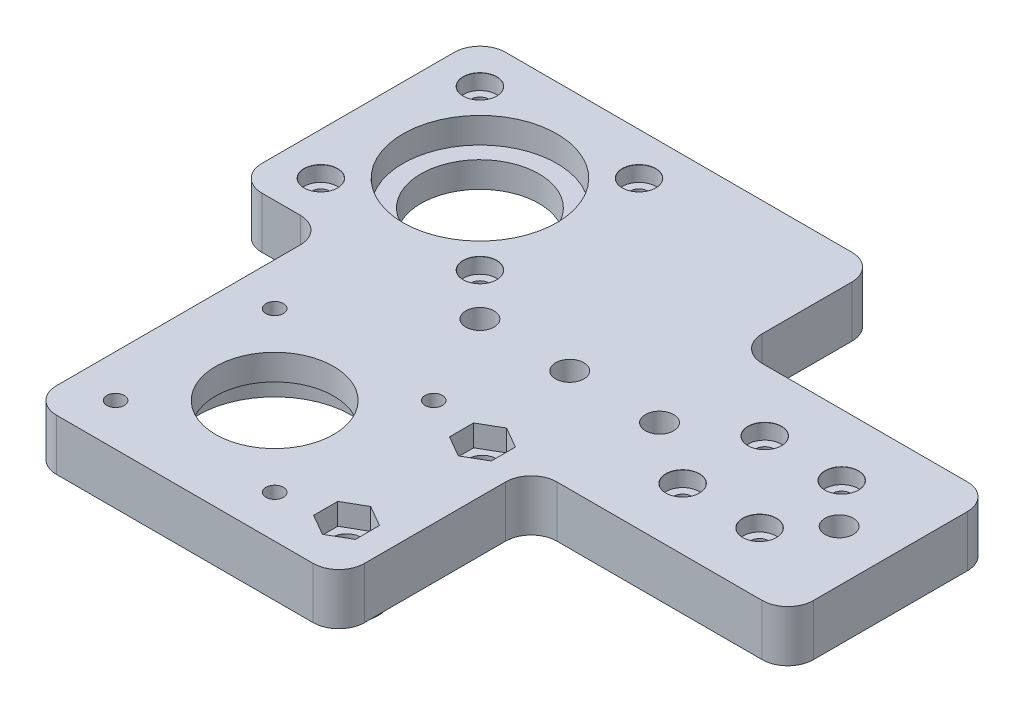
SolidWorks part; units mm, degrees
ref_plane "Front Plane" through (0, 0, 0) normal (0, 0, 1) x (1, 0, 0)
ref_plane "Top Plane" through (0, 0, 0) normal (0, 1, 0) x (1, 0, 0)
ref_plane "Right Plane" through (0, 0, 0) normal (1, 0, 0) x (0, 0, -1)
sketch "Sketch1" plane through (0, 0, 0) normal (0, 1, 0) x (1, 0, 0)
  line L0 (0, 0) -> (110, 0) construction
  line L1 (110, 0) -> (110, 20) construction
  line L2 (110, 20) -> (0, 20) construction
  line L3 (0, 20) -> (0, 0) construction
  line L4 (110, 30) -> (110, -10) construction
  line L5 (110, 30) -> (80, 30) construction
  line L6 (80, 30) -> (80, -10) construction
  line L7 (80, -10) -> (110, -10) construction
  line L8 (0, 67.5) -> (0, -47.5)
  line L16 (0, 67.5) -> (60, 67.5)
  line L18 (0, -47.5) -> (60, -47.5)
  line L19 (60, 67.5) -> (60, 30)
  line L22 (110, -10) -> (60, -10)
  line L23 (60, -10) -> (60, -47.5)
  line L24 (60, 30) -> (110, 30)
  line L25 (110, 30) -> (110, -10)
  point P8 (110, 10)
  point P13 (0, 10)
  dimension "D1" = 20
  dimension "D2" = 37.5
  dimension "D3" = 30
  dimension "D4" = 40
  dimension "D5" = 110
  dimension "D6" = 20
extrude "Boss-Extrude1" add sketch "Sketch1" along normal blind 10
fillet "Fillet1" radius 5 8 edges at (60, 5, -30) (110, 5, -30) (110, 5, 10) (60, 5, 10) (0, 5, 47.5) (0, 5, -67.5) (60, 5, -67.5) (60, 5, 47.5)
sketch "Sketch3" plane through (0, 10, 0) normal (0, 1, 0) x (1, 0, 0)
  line L0 (5, -47.5) -> (55, -47.5) construction
  line L1 (0, 62.5) -> (0, -42.5) construction
  circle A0 centre (23.75, -23.75) radius 11.5
  dimension "D3" = 23
  dimension "D1" = 23.75
  dimension "D2" = 23.75
extrude "Cut-Extrude1" cut sketch "Sketch3" against normal blind 10
sketch "Sketch4" plane through (0, 0, 0) normal (0, -1, 0) x (1, 0, 0)
  line L1 (39.25, 39.25) -> (8.25, 39.25)
  line L2 (39.25, 39.25) -> (39.25, 8.25)
  line L3 (39.25, 8.25) -> (8.25, 8.25)
  line L4 (8.25, 39.25) -> (8.25, 8.25)
  line L5 (39.25, 39.25) -> (8.25, 8.25) construction
  line L6 (39.25, 8.25) -> (8.25, 39.25) construction
  point P0 (23.75, 23.75)
  dimension "D1" = 31
hole_wizard "CBORE for M3 SHCS1" positions "Sketch5" profile "Sketch6" counterbore size "M3" standard "ANSI Metric" end condition through all
sketch "Sketch5" plane through (0, 0, 0) normal (0, -1, 0) x (-1, 0, 0)
  point P0 (-39.25, -8.25)
  point P3 (-8.25, -39.25)
  point P6 (-8.25, -8.25)
  point P9 (-39.25, -39.25)
sketch "Sketch6" plane through (39.25, 0, 8.25) normal (1, 0, 0) x (0, 0, -1)
  line L0 (0, 0) -> (0, 10)
  line L1 (0, 10) -> (1.7, 10)
  line L3 (1.7, 10) -> (1.7, 3)
  line L4 (3.25, 3) -> (1.7, 3)
  line L5 (3.25, 3) -> (3.25, 0.025)
  line L6 (3.25, 0.025) -> (3.275, 0)
  line L7 (3.275, 0) -> (0, 0)
  line L8 (-3.25, 0.025) -> (-3.275, 0) construction
  line L11 (0, -6.35) -> (0, 107.95) construction
  dimension "Thru Hole Dia." = 3.4
  dimension "Thru Hole Depth" = 10
  dimension "C'Bore Dia." = 6.5
  dimension "C'Bore Depth" = 3
  dimension "Near C'Sink Dia." = 6.55
  dimension "Near C'Sink Angle" = 90
sketch "Sketch7" plane through (0, 10, 0) normal (0, 1, 0) x (1, 0, 0)
  line L1 (92.5, 18) -> (77.5, 18)
  line L2 (92.5, 18) -> (92.5, 2)
  line L3 (92.5, 2) -> (77.5, 2)
  line L4 (77.5, 18) -> (77.5, 2)
  line L5 (92.5, 18) -> (77.5, 2) construction
  line L6 (92.5, 2) -> (77.5, 18) construction
  line L7 (110, 10) -> (0, 10)
  line L8 (0, 67.5) -> (0, -47.5) construction
  line L10 (110, 30) -> (110, -10) construction
  point P0 (85, 10)
  dimension "D1" = 15
  dimension "D2" = 16
  dimension "D3" = 25
hole_wizard "CBORE for M3 SHCS2" positions "Sketch8" profile "Sketch9" counterbore size "M3" standard "ANSI Metric" end condition through all
sketch "Sketch8" plane through (0, 10, 0) normal (0, 1, 0) x (1, 0, 0)
  point P0 (77.5, 18)
  point P3 (92.5, 18)
  point P6 (92.5, 2)
  point P9 (77.5, 2)
sketch "Sketch9" plane through (77.5, 10, -18) normal (1, 0, 0) x (0, 0, 1)
  line L0 (0, 0) -> (0, 10)
  line L1 (0, 10) -> (1.7, 10)
  line L3 (1.7, 10) -> (1.7, 3)
  line L4 (3.25, 3) -> (1.7, 3)
  line L5 (3.25, 3) -> (3.25, 0.025)
  line L6 (3.25, 0.025) -> (3.275, 0)
  line L7 (3.275, 0) -> (0, 0)
  line L8 (-3.25, 0.025) -> (-3.275, 0) construction
  line L11 (0, -6.35) -> (0, 107.95) construction
  dimension "Thru Hole Dia." = 3.4
  dimension "Thru Hole Depth" = 10
  dimension "C'Bore Dia." = 6.5
  dimension "C'Bore Depth" = 3
  dimension "Near C'Sink Dia." = 6.55
  dimension "Near C'Sink Angle" = 90
sketch "Sketch10" plane through (0, 0, 0) normal (0, -1, 0) x (1, 0, 0)
  line L0 (110, -10) -> (0, -10) construction
  line L1 (110, 5) -> (110, -25) construction
  line L2 (0, -62.5) -> (0, 42.5) construction
  point P6 (100, -10)
  point P7 (30, -10)
  point P8 (47.5, -10)
  point P9 (65, -10)
  dimension "D1" = 30
  dimension "D2" = 17.5
  dimension "D3" = 17.5
  dimension "D4" = 10
hole_wizard "CBORE for M5 SHCS1" positions "Sketch13" profile "Sketch12" counterbore size "M5" standard "ANSI Metric" end condition through all
sketch "Sketch13" plane through (0, 0, 0) normal (0, -1, 0) x (-1, 0, 0)
  point P0 (-100, 10)
  point P3 (-65, 10)
  point P6 (-47.5, 10)
  point P9 (-30, 10)
sketch "Sketch12" plane through (100, 0, -10) normal (1, 0, 0) x (0, 0, -1)
  line L0 (0, 0) -> (0, 10)
  line L1 (0, 10) -> (2.75, 10)
  line L3 (2.75, 10) -> (2.75, 5)
  line L4 (5, 5) -> (2.75, 5)
  line L5 (5, 5) -> (5, 0.025)
  line L6 (5, 0.025) -> (5.025, 0)
  line L7 (5.025, 0) -> (0, 0)
  line L8 (-5, 0.025) -> (-5.025, 0) construction
  line L11 (0, -6.35) -> (0, 107.95) construction
  dimension "Thru Hole Dia." = 5.5
  dimension "Thru Hole Depth" = 10
  dimension "C'Bore Dia." = 10
  dimension "C'Bore Depth" = 5
  dimension "Near C'Sink Dia." = 10.05
  dimension "Near C'Sink Angle" = 90
sketch "Sketch14" plane through (0, 10, 0) normal (0, 1, 0) x (1, 0, 0)
  line L0 (0, 10) -> (-17.5, 10)
  line L1 (0, 62.5) -> (0, -42.5) construction
  line L2 (-17.5, 10) -> (-17.5, 67.5)
  line L3 (-17.5, 67.5) -> (5, 67.5)
  line L4 (0, 62.5) -> (0, 10)
  arc A0 (5, 67.5) -> (0, 62.5) centre (5, 62.5) ccw construction
  arc A1 (5, 67.5) -> (0, 62.5) centre (5, 62.5) ccw
  dimension "D1" = 17.5
extrude "Boss-Extrude2" add sketch "Sketch14" against normal blind 10
sketch "Sketch15" plane through (0, 10, 0) normal (0, 1, 0) x (1, 0, 0)
  line L0 (-17.5, 67.5) -> (55, 67.5)
  line L1 (-17.5, 67.5) -> (-17.5, 57.5)
  line L2 (-17.5, 67.5) -> (-17.5, 10) construction
  line L3 (-17.5, 57.5) -> (60, 57.5)
  line L5 (60, 35) -> (60, 62.5) construction
  line L6 (60, 57.5) -> (60, 62.5)
  arc A2 (60, 62.5) -> (55, 67.5) centre (55, 62.5) ccw construction
  arc A3 (60, 62.5) -> (55, 67.5) centre (55, 62.5) ccw
  dimension "D1" = 10
extrude "Cut-Extrude2" cut sketch "Sketch15" against normal blind 10
fillet "Fillet2" radius 5 4 edges at (0, 5, -10) (60, 5, -57.5) (-17.5, 5, -57.5) (-17.5, 5, -10)
sketch "Sketch16" plane through (0, 10, 0) normal (0, 1, 0) x (1, 0, 0)
  line L0 (-12.5, 57.5) -> (55, 57.5) construction
  line L1 (-17.5, 52.5) -> (-17.5, 15) construction
  circle A0 centre (6.25, 33.75) radius 11.5
  dimension "D1" = 23
  dimension "D2" = 23.75
  dimension "D3" = 23.75
extrude "Cut-Extrude3" cut sketch "Sketch16" against normal through all
sketch "Sketch17" plane through (0, 10, 0) normal (0, 1, 0) x (1, 0, 0)
  line L1 (21.75, 49.25) -> (-9.25, 49.25)
  line L2 (21.75, 49.25) -> (21.75, 18.25)
  line L3 (21.75, 18.25) -> (-9.25, 18.25)
  line L4 (-9.25, 49.25) -> (-9.25, 18.25)
  line L5 (21.75, 49.25) -> (-9.25, 18.25) construction
  line L6 (21.75, 18.25) -> (-9.25, 49.25) construction
  point P0 (6.25, 33.75)
  dimension "D1" = 31
hole_wizard "CBORE for M3 SHCS3" positions "Sketch18" profile "Sketch19" counterbore size "M3" standard "ANSI Metric" end condition through all
sketch "Sketch18" plane through (0, 10, 0) normal (0, 1, 0) x (1, 0, 0)
  point P0 (-9.25, 49.25)
  point P3 (21.75, 49.25)
  point P6 (21.75, 18.25)
  point P9 (-9.25, 18.25)
sketch "Sketch19" plane through (-9.25, 10, -49.25) normal (1, 0, 0) x (0, 0, 1)
  line L0 (0, 0) -> (0, 10)
  line L1 (0, 10) -> (1.7, 10)
  line L3 (1.7, 10) -> (1.7, 3)
  line L4 (3.25, 3) -> (1.7, 3)
  line L5 (3.25, 3) -> (3.25, 0.025)
  line L6 (3.25, 0.025) -> (3.275, 0)
  line L7 (3.275, 0) -> (0, 0)
  line L8 (-3.25, 0.025) -> (-3.275, 0) construction
  line L11 (0, -6.35) -> (0, 107.95) construction
  dimension "Thru Hole Dia." = 3.4
  dimension "Thru Hole Depth" = 10
  dimension "C'Bore Dia." = 6.5
  dimension "C'Bore Depth" = 3
  dimension "Near C'Sink Dia." = 6.55
  dimension "Near C'Sink Angle" = 90
sketch "Sketch20" plane through (0, 10, 0) normal (0, 1, 0) x (1, 0, 0)
  line L0 (23.75, -23.75) -> (60, -23.75) construction
  line L1 (60, -42.5) -> (60, -15) construction
  line L2 (51, -10.51) -> (51, -36.99) construction
  line L4 (55.0703, -8.16) -> (51, -5.81)
  line L5 (51, -5.81) -> (46.9297, -8.16)
  line L6 (46.9297, -8.16) -> (46.9297, -12.86)
  line L7 (46.9297, -12.86) -> (51, -15.21)
  line L8 (51, -15.21) -> (55.0703, -12.86)
  line L9 (55.0703, -12.86) -> (55.0703, -8.16)
  line L10 (51, -32.29) -> (46.9297, -34.64)
  line L11 (46.9297, -34.64) -> (46.9297, -39.34)
  line L12 (46.9297, -39.34) -> (51, -41.69)
  line L13 (51, -41.69) -> (55.0703, -39.34)
  line L14 (55.0703, -39.34) -> (55.0703, -34.64)
  line L15 (55.0703, -34.64) -> (51, -32.29)
  line L18 (0, 5) -> (0, -42.5) construction
  circle A0 centre (51, -10.51) radius 4.0703 construction
  circle A1 centre (51, -36.99) radius 4.0703 construction
  point P8 (51, -23.75)
  point P25 (51, -36.99)
  point P26 (51, -10.51)
  dimension "D1" = 26.48
  dimension "D2" = 9
  dimension "D3" = 4.7
extrude "Cut-Extrude4" cut sketch "Sketch20" against normal blind 4.2
hole_wizard "M5 Clearance Hole1" positions "Sketch22" profile "Sketch23" hole size "M5" standard "ANSI Metric" end condition through all
sketch "Sketch22" plane through (0, 10, 0) normal (0, 1, 0) x (1, 0, 0)
  point P0 (51, -10.51)
  point P3 (51, -36.99)
sketch "Sketch23" plane through (51, 10, 10.51) normal (1, 0, 0) x (0, 0, 1)
  line L0 (0, 0) -> (0, 10)
  line L1 (0, 10) -> (2.75, 10)
  line L2 (2.75, 10) -> (2.75, 0.025)
  line L3 (2.75, 0.025) -> (2.775, 0)
  line L5 (2.775, 0) -> (0, 0)
  line L6 (-2.75, 0.025) -> (-2.775, 0) construction
  line L11 (0, -6.35) -> (0, 107.95) construction
  dimension "Thru Hole Dia." = 5.5
  dimension "Thru Hole Depth" = 10
  dimension "Near C'Sink Dia." = 5.55
  dimension "Near C'Sink Angle" = 90
sketch "Sketch24" plane through (0, 10, 0) normal (0, 1, 0) x (1, 0, 0)
  circle A0 centre (6.25, 33.75) radius 15
  dimension "D1" = 30
extrude "Cut-Extrude5" cut sketch "Sketch24" against normal blind 5
sketch "Sketch25" plane through (0, 0, 0) normal (0, -1, 0) x (1, 0, 0)
  circle A0 centre (23.75, 23.75) radius 15
  dimension "D1" = 30
extrude "Cut-Extrude6" cut sketch "Sketch25" against normal blind 5
sketch "Sketch26" plane through (0, 0, 0) normal (0, -1, 0) x (1, 0, 0)
  circle A0 centre (51, 36.99) radius 6.25
  circle A1 centre (51, 36.99) radius 2.75 construction
  circle A2 centre (51, 36.99) radius 2.75
  circle A3 centre (51, 10.51) radius 6.25
  circle A4 centre (51, 10.51) radius 2.75 construction
  circle A5 centre (51, 10.51) radius 2.75
  dimension "D1" = 12.5
extrude "Boss-Extrude3" add sketch "Sketch26" along normal blind 2.9
